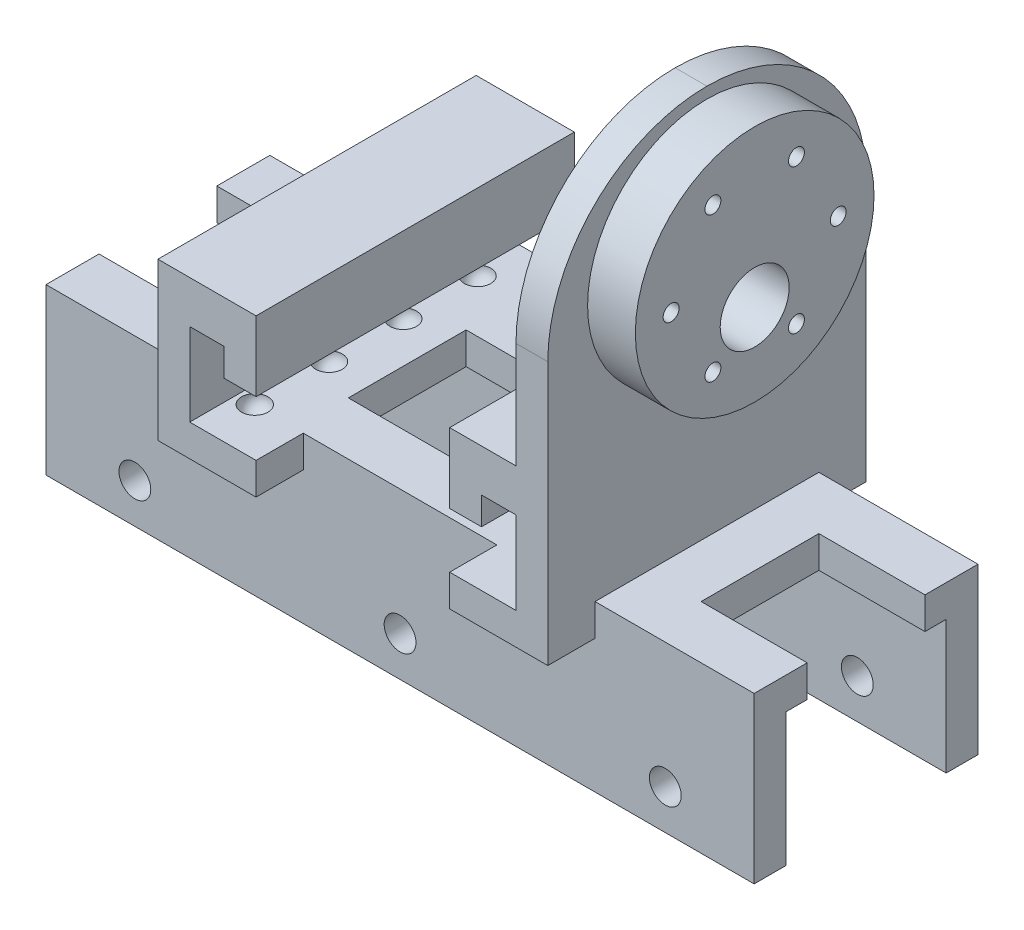
SolidWorks part; units mm, degrees
material "Nylon 101"
ref_plane "Front Plane" through (0, 0, 0) normal (0, 0, 1) x (1, 0, 0)
ref_plane "Top Plane" through (0, 0, 0) normal (0, 1, 0) x (1, 0, 0)
ref_plane "Right Plane" through (0, 0, 0) normal (1, 0, 0) x (0, 0, -1)
sketch "Sketch1" plane through (0, 0, 0) normal (0, 0, 1) x (1, 0, 0)
  line L0 (0, 29.6) -> (0, 0)
  line L1 (0, 0) -> (73.5, 0)
  line L2 (73.5, 0) -> (73.5, 79.6)
  line L3 (73.5, 79.6) -> (67.5, 79.6)
  line L4 (67.5, 79.6) -> (67.5, 29.6)
  line L5 (67.5, 6) -> (6, 6)
  line L6 (6, 6) -> (6, 21.6)
  line L7 (6, 21.6) -> (12.5, 21.6)
  line L8 (0, 29.6) -> (18.5, 29.6)
  line L10 (12.5, 21.6) -> (12.5, 16.4)
  line L11 (12.5, 16.4) -> (18.5, 16.4)
  line L12 (18.5, 16.4) -> (18.5, 29.6)
  line L13 (67.5, 29.6) -> (55, 29.6)
  line L14 (55, 29.6) -> (55, 16.4)
  line L15 (55, 16.4) -> (61, 16.4)
  line L16 (61, 16.4) -> (61, 21.6)
  line L17 (61, 21.6) -> (67.5, 21.6)
  line L18 (67.5, 21.6) -> (67.5, 6)
  dimension "D1" = 8
  dimension "D2" = 6
  dimension "D3" = 6
  dimension "D4" = 5.2
  dimension "D5" = 15.6
  dimension "D6" = 6
  dimension "D7" = 6.5
  dimension "D8" = 6.5
  dimension "D9" = 6
  dimension "D10" = 61.5
  dimension "D11" = 6
  dimension "D12" = 50
extrude "Boss-Extrude1" add sketch "Sketch1" along normal blind 60
sketch "Sketch2" plane through (67.5, 0, 0) normal (-1, 0, 0) x (0, 0, 1)
  circle A0 centre (30, 55) radius 15.75 construction
  circle A1 centre (45.75, 55) radius 1.5
  dimension "D3" = 31.5
  dimension "D2" = 55
  dimension "D4" = 3
  dimension "D1" = 30
extrude "Cut-Extrude1" cut sketch "Sketch2" against normal blind 6
sketch "Sketch3" plane through (0, 21.6, 0) normal (0, -1, 0) x (1, 0, 0)
  line L0 (61.75, 51) -> (66.75, 51)
  line L2 (0, 60) -> (73.5, 60) construction
  line L4 (61, 60) -> (61, 0) construction
  arc A0 (66.75, 51) -> (61.75, 51) centre (64.25, 51) ccw
  dimension "D1" = 5
  dimension "D2" = 9
  dimension "D3" = 3.25
revolve "Cut-Revolve1" cut sketch "Sketch3" angle 360 about L0
pattern_linear "LPattern1" count 4 spacing 14 along (0, 0, -1) count 2 spacing 55 along (-1, 0, 0) of "Cut-Revolve1"
sketch "Sketch4" plane through (73.5, 0, 0) normal (1, 0, 0) x (0, 0, -1)
  line L0 (-60, 0) -> (-60, 79.6) construction
  line L1 (-51.1, 6) -> (-8.9, 6)
  line L2 (-51.1, 6) -> (-51.1, 0)
  line L3 (-51.1, 0) -> (-8.9, 0)
  line L4 (-8.9, 6) -> (-8.9, 0)
  line L5 (-51.1, 6) -> (-8.9, 0) construction
  line L6 (-51.1, 0) -> (-8.9, 6) construction
  line L7 (-60, 0) -> (0, 0) construction
  point P0 (-30, 3)
  dimension "D1" = 6
  dimension "D2" = 42.2
  dimension "D3" = 8.9
extrude "Boss-Extrude2" add sketch "Sketch4" along normal blind 50
sketch "Sketch5" plane through (0, 0, 0) normal (-1, 0, 0) x (0, 0, 1)
  line L0 (60, 0) -> (0, 0) construction
  line L1 (8.9, 6) -> (51.1, 6)
  line L2 (8.9, 6) -> (8.9, 0)
  line L3 (8.9, 0) -> (51.1, 0)
  line L4 (51.1, 6) -> (51.1, 0)
  line L5 (8.9, 6) -> (51.1, 0) construction
  line L6 (8.9, 0) -> (51.1, 6) construction
  point P0 (30, 3)
  dimension "D1" = 42.2
  dimension "D2" = 6
  dimension "D3" = 8.9
extrude "Boss-Extrude3" add sketch "Sketch5" along normal blind 50
sketch "Sketch6" plane through (0, 0, 0) normal (0, -1, 0) x (1, 0, 0)
  line L0 (-50, 51.1) -> (0, 51.1) construction
  line L1 (-50, 51.1) -> (123.5, 51.1)
  line L2 (-50, 51.1) -> (-50, 45.1)
  line L3 (-50, 45.1) -> (123.5, 45.1)
  line L4 (123.5, 51.1) -> (123.5, 45.1)
  line L5 (-50, 51.1) -> (123.5, 45.1) construction
  line L6 (-50, 45.1) -> (123.5, 51.1) construction
  line L8 (123.5, 51.1) -> (123.5, 8.9) construction
  line L10 (-50, 8.9) -> (123.5, 8.9)
  line L11 (-50, 8.9) -> (-50, 14.9)
  line L12 (-50, 14.9) -> (123.5, 14.9)
  line L13 (123.5, 8.9) -> (123.5, 14.9)
  line L14 (-50, 8.9) -> (123.5, 14.9) construction
  line L15 (-50, 14.9) -> (123.5, 8.9) construction
  line L16 (123.5, 8.9) -> (73.5, 8.9) construction
  line L17 (-50, 8.9) -> (-50, 51.1) construction
  point P0 (36.75, 48.1)
  point P11 (36.75, 11.9)
  dimension "D1" = 6
extrude "Boss-Extrude4" add sketch "Sketch6" along normal blind 25.1
ref_plane "Plane1" through (36.75, 0, 0) normal (-1, 0, 0) x (0, 0, 1)
ref_axis "Axis1" through (67.5, 55, 30) along (-1, 0, 0)
pattern_circular "CirPattern2" count 6 over 360 about axis through (67.5, 55, 30) along (-1, 0, 0) of "Cut-Extrude1"
sketch "Sketch10" plane through (67.5, 0, 0) normal (-1, 0, 0) x (0, 0, 1)
  circle A0 centre (30, 48) radius 6.5
  dimension "D1" = 13
  dimension "D2" = 7
extrude "Cut-Extrude4" cut sketch "Sketch10" against normal blind 10
sketch "Sketch11" plane through (73.5, 0, 0) normal (1, 0, 0) x (0, 0, -1)
  circle A0 centre (-30, 55) radius 22.5
  circle A1 centre (-37.875, 68.6399) radius 1.5 construction
  circle A2 centre (-22.125, 68.6399) radius 1.5 construction
  circle A3 centre (-14.25, 55) radius 1.5 construction
  circle A4 centre (-22.125, 41.3601) radius 1.5 construction
  circle A5 centre (-30, 48) radius 6.5 construction
  circle A6 centre (-37.875, 41.3601) radius 1.5 construction
  circle A7 centre (-45.75, 55) radius 1.5 construction
  circle A8 centre (-37.875, 68.6399) radius 1.5
  circle A9 centre (-22.125, 68.6399) radius 1.5
  circle A10 centre (-14.25, 55) radius 1.5
  circle A11 centre (-22.125, 41.3601) radius 1.5
  circle A12 centre (-30, 48) radius 6.5
  circle A13 centre (-37.875, 41.3601) radius 1.5
  circle A14 centre (-45.75, 55) radius 1.5
  dimension "D1" = 45
extrude "Boss-Extrude6" add sketch "Sketch11" along normal blind 9
sketch "Sketch12" plane through (0, 0, 8.9) normal (0, 0, -1) x (-1, 0, 0)
  line L0 (-36.75, -33) -> (-36.75, 33) construction
  line L1 (50, -25.1) -> (-123.5, -25.1) construction
  circle A0 centre (-36.75, -17.6) radius 3
  circle A1 centre (-86.75, -17.6) radius 3
  circle A2 centre (13.25, -17.6) radius 3
  dimension "D2" = 6
  dimension "D4" = 7.5
  dimension "D5" = 6
  dimension "D7" = 6
  dimension "D1" = 7.5
  dimension "D3" = 50
  dimension "D6" = 50
  dimension "D8" = 7.5
extrude "Cut-Extrude5" cut sketch "Sketch12" against normal through all
ref_plane "Plane2" through (0, 13.8, 0) normal (0, -1, 0) x (-1, 0, 0)
mirror "Mirror2" about plane through (0, 13.8, 0) normal (0, -1, 0) of "LPattern1", "Cut-Revolve1"
sketch "Sketch13" plane through (0, 6, 0) normal (0, 1, 0) x (1, 0, 0)
  line L0 (0, -51.1) -> (0, -8.9) construction
  line L1 (0, -8.9) -> (-50, -8.9) construction
  line L2 (-50, -8.9) -> (-50, -51.1) construction
  line L3 (-50, -51.1) -> (0, -51.1) construction
  line L4 (73.5, -8.9) -> (73.5, -51.1) construction
  line L5 (73.5, -51.1) -> (123.5, -51.1) construction
  line L6 (123.5, -51.1) -> (123.5, -8.9) construction
  line L7 (123.5, -8.9) -> (73.5, -8.9) construction
  line L8 (0, -51.1) -> (0, -8.9)
  line L9 (0, -8.9) -> (-50, -8.9)
  line L10 (-50, -8.9) -> (-50, -51.1)
  line L11 (-50, -51.1) -> (0, -51.1)
  line L12 (73.5, -8.9) -> (73.5, -51.1)
  line L13 (73.5, -51.1) -> (123.5, -51.1)
  line L14 (123.5, -51.1) -> (123.5, -8.9)
  line L15 (123.5, -8.9) -> (73.5, -8.9)
  line L16 (-40, -18.9) -> (-40, -41.1)
  line L17 (-40, -41.1) -> (-10, -41.1)
  line L18 (-10, -41.1) -> (-10, -18.9)
  line L19 (-10, -18.9) -> (-40, -18.9)
  line L20 (113.5, -18.9) -> (83.5, -18.9)
  line L21 (83.5, -18.9) -> (83.5, -41.1)
  line L22 (83.5, -41.1) -> (113.5, -41.1)
  line L23 (113.5, -41.1) -> (113.5, -18.9)
  dimension "D1" = 10
extrude "Cut-Extrude6" cut sketch "Sketch13" against normal blind 10 contours L18 L19 L16 L17 | L22 L23 L20 L21 region at (-25, 6, 30) region at (98.5, 6, 30)
sketch "Sketch14" plane through (0, 6, 0) normal (0, 1, 0) x (1, 0, 0)
  line L0 (83.5, -41.1) -> (113.5, -41.1) construction
  line L1 (17, -18.9) -> (57, -18.9)
  line L2 (17, -18.9) -> (17, -41.1)
  line L3 (17, -41.1) -> (57, -41.1)
  line L4 (67.5, 0) -> (6, 0)
  line L5 (6, 0) -> (6, -60)
  line L6 (6, -60) -> (67.5, -60)
  line L7 (67.5, -60) -> (67.5, 0)
  line L8 (67.5, 0) -> (6, 0)
  line L9 (6, 0) -> (6, -60)
  line L10 (6, -60) -> (67.5, -60)
  line L11 (67.5, -60) -> (67.5, 0)
  line L12 (57, -18.9) -> (57, -41.1)
  line L13 (113.5, -18.9) -> (83.5, -18.9) construction
  dimension "D2" = 40
  dimension "D3" = 10.5
  dimension "D1" = 0
extrude "Cut-Extrude7" cut sketch "Sketch14" against normal blind 10 contours L12 L1 L2 L3 region at (37, 6, 30)
fillet "Fillet1" radius 30 2 edges at (70.5, 79.6, 60) (70.5, 79.6, 0)
sketch "Sketch15" plane through (0, 0, 0) normal (0, -1, 0) x (1, 0, 0)
  line L0 (18.5, 60) -> (18.5, 0) construction
  line L1 (55, 60) -> (55, 0) construction
  line L2 (18.5, 60) -> (18.5, 0)
  line L3 (55, 60) -> (55, 0)
  line L4 (18.5, 60) -> (55, 60)
  line L5 (55, 51.1) -> (18.5, 51.1)
  line L6 (73.5, 51.1) -> (0, 51.1) construction
  line L7 (18.5, 0) -> (55, 0)
  line L8 (55, 8.9) -> (18.5, 8.9)
  line L9 (0, 8.9) -> (73.5, 8.9) construction
  line M1 (0, 51.1) -> (73.5, 51.1)
  line M3 (73.5, 60) -> (0, 60)
extrude "Cut-Extrude8" cut sketch "Sketch15" against normal blind 10 contours L3 L2 M3 M1 | L3 L8 L2 L7 region at (36.75, 0, 55.55) region at (36.75, 0, 4.45)
sketch "Sketch16" plane through (0, 0, 51.1) normal (0, 0, 1) x (1, 0, 0)
  line L0 (-30, -25.1) -> (-30, 6)
  line L1 (123.5, -25.1) -> (-50, -25.1) construction
  line L2 (-50, 6) -> (0, 6) construction
  line L3 (103.5, -25.1) -> (103.5, 6)
  line L4 (123.5, 6) -> (73.5, 6) construction
  line L5 (103.5, 6) -> (123.5, 6)
  line L6 (123.5, 6) -> (123.5, -25.1)
  line L7 (123.5, -25.1) -> (103.5, -25.1)
  line L8 (-30, -25.1) -> (-50, -25.1)
  line L9 (-50, -25.1) -> (-50, 6)
  line L10 (-50, 6) -> (-30, 6)
  dimension "D1" = 20
extrude "Cut-Extrude9" cut sketch "Sketch16" against normal through all
